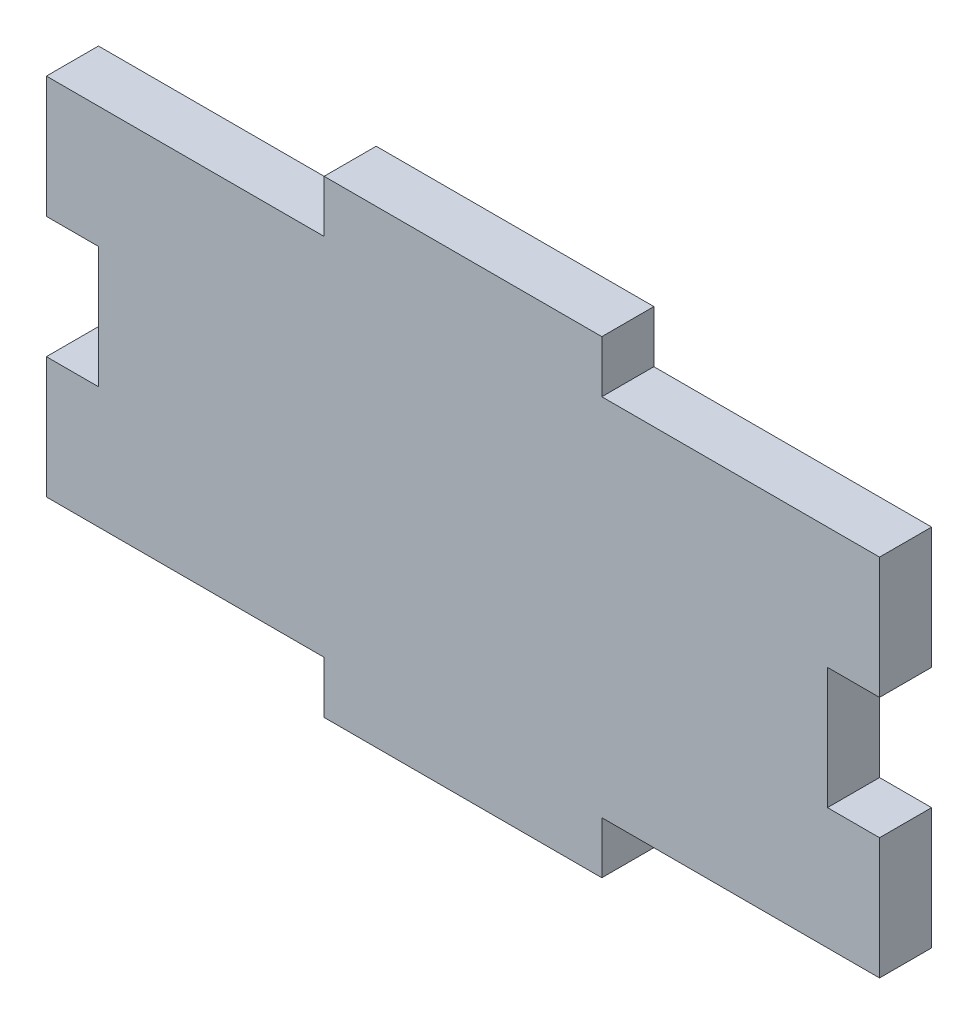
SolidWorks part; units mm, degrees
ref_plane "Front Plane" through (0, 0, 0) normal (0, 0, 1) x (1, 0, 0)
ref_plane "Top Plane" through (0, 0, 0) normal (0, 1, 0) x (1, 0, 0)
ref_plane "Right Plane" through (0, 0, 0) normal (1, 0, 0) x (0, 0, -1)
sketch "Sketch1" plane through (0, 0, 0) normal (0, 0, 1) x (1, 0, 0)
  line L0 (-24, 10.5) -> (-8, 10.5)
  line L1 (-8, 10.5) -> (-8, 13.5)
  line L2 (-8, 13.5) -> (8, 13.5)
  line L3 (8, 13.5) -> (8, 10.5)
  line L4 (8, 10.5) -> (24, 10.5)
  line L5 (24, 10.5) -> (24, 3.5)
  line L6 (24, 3.5) -> (21, 3.5)
  line L7 (21, 3.5) -> (21, -3.5)
  line L8 (21, -3.5) -> (24, -3.5)
  line L9 (24, -3.5) -> (24, -10.5)
  line L10 (55, 0) -> (-55, 0) construction
  line L11 (8, -10.5) -> (24, -10.5)
  line L12 (8, -13.5) -> (8, -10.5)
  line L13 (-8, -13.5) -> (8, -13.5)
  line L14 (-8, -10.5) -> (-8, -13.5)
  line L15 (-24, -10.5) -> (-8, -10.5)
  line L16 (0, -55) -> (0, 55) construction
  line L17 (-24, -3.5) -> (-24, -10.5)
  line L18 (-21, -3.5) -> (-24, -3.5)
  line L19 (-21, 3.5) -> (-21, -3.5)
  line L20 (-24, 3.5) -> (-21, 3.5)
  line L21 (-24, 10.5) -> (-24, 3.5)
  point P8 (0, 13.5)
  point P12 (15.6066, -3.8033)
  point P14 (18.0984, -5.5082)
  point P15 (21, 0)
  point P29 (8, 10.3235)
  dimension "D1" = 16
  dimension "D2" = 21
  dimension "D3" = 3
extrude "Boss-Extrude1" add sketch "Sketch1" along normal blind 3 contours L0 L1 L2 L3 L4 L5 L6 L7 L8 L9 L11 L12 L13 L14 L15 L17 L18 L19 L20 L21
